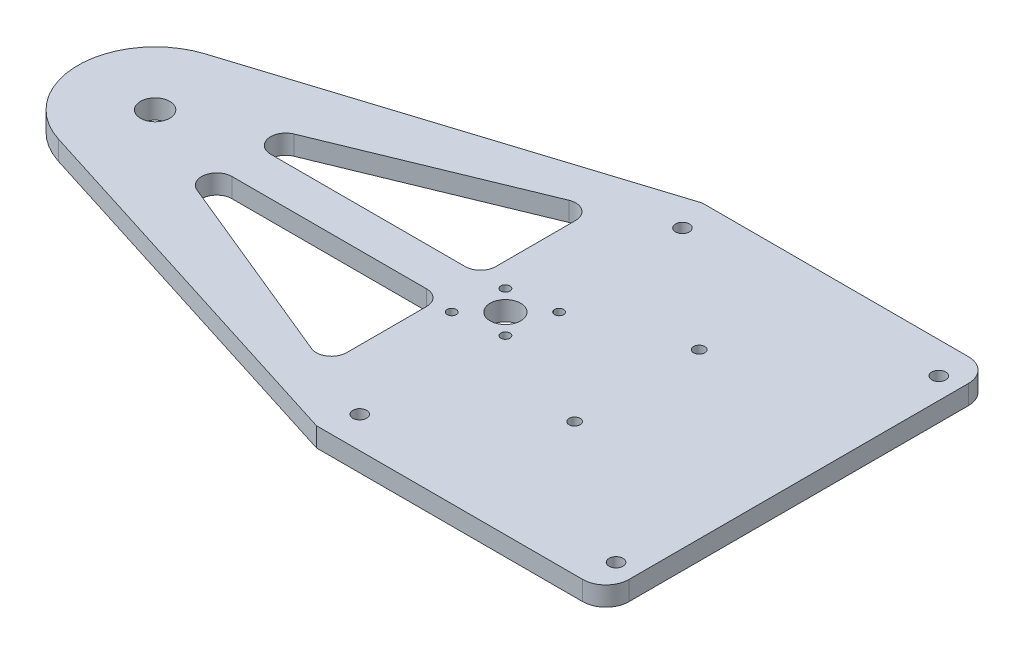
SolidWorks part; units mm, degrees
material "UHMW"
ref_plane "Front Plane" through (0, 0, 0) normal (0, 0, 1) x (1, 0, 0)
ref_plane "Top Plane" through (0, 0, 0) normal (0, 1, 0) x (1, 0, 0)
ref_plane "Right Plane" through (0, 0, 0) normal (1, 0, 0) x (0, 0, -1)
sketch "Sketch1" plane through (0, 0, 0) normal (0, 1, 0) x (1, 0, 0)
  line L0 (-47.625, 0) -> (47.625, 0) construction
  line L1 (-47.625, -63.5) -> (47.625, -63.5)
  line L2 (-47.625, -63.5) -> (-47.625, 63.5)
  line L3 (-47.625, 63.5) -> (47.625, 63.5)
  line L4 (47.625, -63.5) -> (47.625, 63.5)
  line L5 (-47.625, -63.5) -> (47.625, 63.5) construction
  line L6 (-47.625, 63.5) -> (47.625, -63.5) construction
  point P0 (0, 0)
  dimension "D1" = 95.25
  dimension "D2" = 127
  dimension "D3" = 63.5
extrude "Boss-Extrude1" add sketch "Sketch1" along normal blind 6.35
sketch "Sketch4" plane through (0, 6.35, 0) normal (0, 1, 0) x (1, 0, 0)
  line L1 (-47.625, 63.5) -> (-171.916, 24.2193)
  line L5 (-47.625, 63.5) -> (-47.625, -63.5) construction
  line L9 (-47.625, -63.5) -> (-171.916, -24.2193)
  line L10 (-47.625, 63.5) -> (-47.625, -63.5)
  arc A0 (-171.916, 24.2193) -> (-171.916, -24.2193) centre (-164.2618, 0) ccw
  circle A1 centre (-48.9458, 0) radius 2.5 construction
  dimension "D1" = 50.8
  dimension "D2" = 115.316
extrude "Boss-Extrude3" add sketch "Sketch4" against normal blind 6.35
sketch "Sketch5" plane through (0, 6.35, 0) normal (0, 1, 0) x (1, 0, 0)
  line L0 (-48.9458, 0) -> (-31.7264, 0) construction
  line L3 (-48.9458, 0) -> (-91.3931, 0) construction
  circle A0 centre (-164.2618, 0) radius 4.826
  circle A1 centre (-48.9458, 0) radius 5.04
  arc A2 (-171.916, 24.2193) -> (-171.916, -24.2193) centre (-164.2618, 0) ccw construction
  arc A3 (-171.916, 24.2193) -> (-171.916, -24.2193) centre (-164.2618, 0) ccw
  circle A4 centre (-42.2283, -6.7175) radius 1.5
  circle A5 centre (-40.107, 8.8388) radius 1.5
  circle A6 centre (-57.7846, -8.8388) radius 1.5
  circle A7 centre (-55.6633, 6.7175) radius 1.5
  circle A8 centre (-40.107, 8.8388) radius 1.5 construction
  circle A9 centre (-55.6633, 6.7175) radius 1.5 construction
  circle A10 centre (-57.7846, -8.8388) radius 1.5 construction
  circle A11 centre (-42.2283, -6.7175) radius 1.5 construction
  point P20 (-48.9458, 0)
  dimension "D1" = 9.652
  dimension "D2" = 17.2194
  dimension "D4" = 48.9458
  dimension "D3" = 10.08
extrude "Cut-Extrude1" cut sketch "Sketch5" against normal through all contours A0 | A1 | A5 | A6 | A7 | A4 region at (-164.2618, 6.35, 0) region at (-48.9458, 6.35, 0)
sketch "Sketch6" plane through (0, 6.35, 0) normal (0, 1, 0) x (1, 0, 0)
  line L0 (-63.5, 6.35) -> (-63.5, -6.35) construction
  line L1 (-63.5, 45.1637) -> (-157.9118, 6.35)
  line L2 (-157.9118, 6.35) -> (-63.5, 6.35)
  line L3 (-63.5, 6.35) -> (-63.5, 45.1637)
  line L4 (-63.5, -6.35) -> (-63.5, -45.1637)
  line L5 (-63.5, -45.1637) -> (-157.9118, -6.35)
  line L6 (-157.9118, -6.35) -> (-63.5, -6.35)
  line L7 (0, 0) -> (-63.5, 0) construction
  line L8 (-189.6618, 75.5498) -> (-189.6618, -75.5498) construction
  line L9 (-47.625, 63.5) -> (-171.916, 24.2193) construction
  arc A0 (-171.916, 24.2193) -> (-171.916, -24.2193) centre (-164.2618, 0) ccw construction
  point P12 (-189.6618, 0)
  dimension "D1" = 31.75
  dimension "D2" = 12.7
  dimension "D3" = 12.7
  dimension "D4" = 63.5
extrude "Cut-Extrude2" cut sketch "Sketch6" against normal through all
fillet "Fillet9" radius 5 6 edges at (-157.9118, 3.175, 6.35) (-63.5, 3.175, 6.35) (-63.5, 3.175, 45.1637) (-63.5, 3.175, -6.35) (-157.9118, 3.175, -6.35) (-63.5, 3.175, -45.1637)
fillet "Fillet10" radius 7.62 2 edges at (47.625, 3.175, -63.5) (47.625, 3.175, 63.5)
sketch "Sketch7" plane through (0, 6.35, 0) normal (0, 1, 0) x (1, 0, 0)
  circle A0 centre (-43.7773, -53.1254) radius 2.2812
  circle A1 centre (-43.7773, 53.1254) radius 2.2812
  circle A2 centre (40.6023, 53.1254) radius 2.2812
  circle A3 centre (40.6023, -53.1254) radius 2.2812
  circle A4 centre (-43.7773, 53.1254) radius 2.2812 construction
  circle A5 centre (40.6023, 53.1254) radius 2.2812 construction
  circle A6 centre (40.6023, -53.1254) radius 2.2812 construction
  circle A7 centre (-43.7773, -53.1254) radius 2.2812 construction
extrude "Cut-Extrude3" cut sketch "Sketch7" against normal through all
sketch "Sketch8" plane through (0, 6.35, 0) normal (0, 1, 0) x (1, 0, 0)
  circle A0 centre (-6.3285, -19.8289) radius 1.83
  circle A1 centre (-6.3283, 21.1715) radius 1.83
  circle A2 centre (-6.3285, -19.8289) radius 1.83 construction
  circle A3 centre (-6.3283, 21.1715) radius 1.83 construction
extrude "Cut-Extrude4" cut sketch "Sketch8" against normal through all
